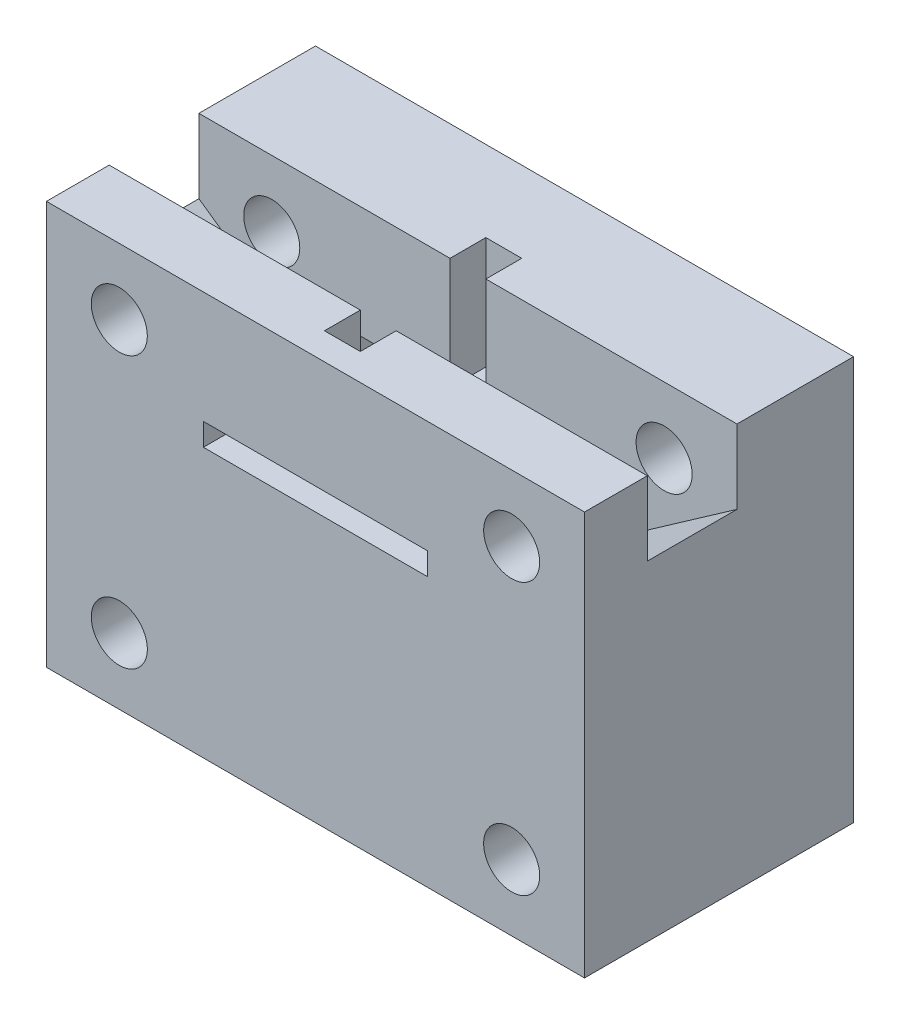
SolidWorks part; units mm, degrees
ref_plane "Front Plane" through (0, 0, 0) normal (0, 0, 1) x (1, 0, 0)
ref_plane "Top Plane" through (0, 0, 0) normal (0, 1, 0) x (1, 0, 0)
ref_plane "Right Plane" through (0, 0, 0) normal (1, 0, 0) x (0, 0, -1)
sketch "Sketch1" plane through (0, 0, 0) normal (0, 0, 1) x (1, 0, 0)
  line L0 (60, 0) -> (60, 97.0379) construction
  line L1 (0, 0) -> (120, 0)
  line L2 (0, 0) -> (0, 90)
  line L3 (0, 90) -> (120, 90)
  line L4 (120, 0) -> (120, 90)
  line L5 (0, 45) -> (130.8057, 45) construction
  line L6 (16.25, 75.25) -> (103.75, 75.25) construction
  line L7 (16.25, 75.25) -> (16.25, 14.75) construction
  circle A0 centre (16.25, 75.25) radius 3.25
  circle A1 centre (103.75, 75.25) radius 3.25
  circle A2 centre (103.75, 14.75) radius 3.25
  circle A3 centre (16.25, 14.75) radius 3.25
  dimension "D5" = 6.5
  dimension "D1" = 120
  dimension "D2" = 90
  dimension "D3" = 87.5
  dimension "D4" = 60.5
extrude "Boss-Extrude1" add sketch "Sketch1" along normal blind 60
sketch "Sketch2" plane through (0, 90, 0) normal (0, 1, 0) x (1, 0, 0)
  line L0 (120, -60) -> (120, 0) construction
  line L1 (0, 0) -> (120, 0)
  line L2 (0, 0) -> (0, -12)
  line L3 (0, -12) -> (120, -12)
  line L4 (120, 0) -> (120, -12)
  line L5 (0, -12) -> (0, -60)
  line L6 (0, -36) -> (120, -36) construction
  line L7 (45, -46) -> (45, -26)
  line L8 (45, -46) -> (75, -46)
  line L9 (45, -26) -> (75, -26)
  line L10 (75, -46) -> (75, -26)
  line L11 (45, -46) -> (75, -26) construction
  line L12 (45, -26) -> (75, -46) construction
  line L22 (56, -18) -> (64, -18)
  line L23 (56, -46) -> (64, -46)
  line L24 (56, -46) -> (56, -54)
  line L25 (56, -54) -> (64, -54)
  line L26 (64, -46) -> (64, -54)
  line L27 (64, -26) -> (64, -18)
  line L28 (56, -26) -> (64, -26)
  line L29 (56, -26) -> (56, -18)
  point P12 (60, -36)
  point P20 (60, -46)
  dimension "D1" = 12
  dimension "D2" = 30
  dimension "D3" = 20
  dimension "D4" = 8
  dimension "D5" = 8
extrude "Cut-Extrude1" cut sketch "Sketch2" against normal blind 30 contours L8 L10 L9 L7 | L29 L9 L27 L22 | L26 L8 L24 L25 region at (60, 90, 36) region at (60, 90, 50) region at (60, 90, 22)
sketch "Sketch3" plane through (0, 0, 60) normal (0, 0, 1) x (1, 0, 0)
  line L0 (120, 0) -> (120, 90) construction
  line L1 (0, 90) -> (120, 90)
  line L2 (0, 90) -> (0, 60)
  line L3 (0, 60) -> (120, 60)
  line L4 (120, 90) -> (120, 60)
  line L5 (0, 68) -> (120, 68)
  line L6 (64.25, 90) -> (55.75, 90)
  line L7 (64.25, 90) -> (64.25, 60)
  line L8 (64.25, 60) -> (55.75, 60)
  line L9 (55.75, 90) -> (55.75, 60)
  line L10 (45, 60) -> (56, 60) construction
  line L11 (35, 65) -> (85, 65)
  line L12 (35, 65) -> (35, 60)
  line L13 (35, 60) -> (85, 60)
  line L14 (85, 65) -> (85, 60)
  point P11 (60, 90)
  point P19 (60, 60)
  dimension "D2" = 8.5
  dimension "D3" = 8
  dimension "D4" = 50
  dimension "D5" = 5
extrude "Cut-Extrude2" cut sketch "Sketch3" against normal up to surface (14 mm away) contours L14 L11 L7 L3 | L11 L12 L3 L9 | L12 L11 L14 L13 region at (45.375, 62.5, 60) region at (74.625, 62.5, 60) up to face at (50.5, 75, 46)
ref_plane "Plane1" through (0, 0, 36) normal (0, 0, 1) x (1, 0, 0)
sketch "Sketch5" plane through (0, 0, 0) normal (0, 0, -1) x (-1, 0, 0)
  line L0 (-35, 65) -> (-35, 60) construction
  line L1 (-35, 65) -> (-85, 65) construction
  line L2 (-85, 65) -> (-85, 60) construction
  line L3 (-35, 60) -> (-85, 60) construction
  line L4 (0, 0) -> (0, 90)
  line L5 (0, 90) -> (-120, 90)
  line L6 (-120, 90) -> (-120, 0)
  line L7 (-120, 0) -> (0, 0)
  line L8 (0, 0) -> (0, 90)
  line L9 (0, 90) -> (-120, 90)
  line L10 (-120, 90) -> (-120, 0)
  line L11 (-120, 0) -> (0, 0)
  line L12 (-35, 65) -> (-35, 60)
  line L13 (-35, 65) -> (-85, 65)
  line L14 (-85, 65) -> (-85, 60)
  line L15 (-35, 60) -> (-85, 60)
  dimension "D1" = 0
extrude "Cut-Extrude5" cut sketch "Sketch5" against normal up to surface (26 mm away) contours L15 L12 L13 L14 region at (60, 62.5, 0) up to face at (69.5, 75, 26)
sketch "Sketch6" plane through (0, 60, 0) normal (0, 1, 0) x (1, 0, 0)
  line L1 (45, -26) -> (75, -26)
  line L2 (45, -26) -> (45, -46)
  line L3 (45, -46) -> (75, -46)
  line L4 (75, -26) -> (75, -46)
extrude "Cut-Extrude6" cut sketch "Sketch6" against normal blind 18
sketch "Sketch7" plane through (0, 0, 26) normal (0, 0, 1) x (1, 0, 0)
  line L0 (75, 42) -> (120, 73.5093)
  line L1 (120, 0) -> (120, 90) construction
  line L2 (120, 42) -> (138.0601, 42) construction
  line L3 (0, 90) -> (0, 73.5093)
  line L5 (60, 63.8) -> (60, 175.0062) construction
  line L6 (0, 90) -> (120, 90)
  line L7 (60, 90) -> (60, 42)
  line L8 (45, 42) -> (75, 42)
  line L9 (120, 90) -> (120, 73.5093)
  line L10 (45, 42) -> (0, 73.5093)
  line M5 (64, 65) -> (75, 65)
  line M6 (75, 65) -> (75, 90)
  line M8 (64, 90) -> (64, 65)
  dimension "D1" = 35
extrude "Cut-Extrude7" cut sketch "Sketch7" along normal up to surface (20 mm away) contours L10 L8 L7 L6 L3 | L9 L6 L7 L8 L0 M6 M5 M8 region at (87.3646, 69.3788, 26) region at (34.8983, 70.4075, 26) up to face at (50.5, 77.5, 46)
sketch "Sketch8" plane through (0, 0, 60) normal (0, 0, 1) x (1, 0, 0)
  line L0 (0, 45) -> (120, 45)
  line L1 (0, 90) -> (0, 0) construction
  line L2 (120, 0) -> (120, 90) construction
  line L3 (60, 0) -> (60, 90)
  line L4 (0, 0) -> (120, 0) construction
  line L5 (120, 90) -> (0, 90) construction
  circle A0 centre (16.25, 75.25) radius 6.25
  circle A1 centre (16.25, 75.25) radius 3.25 construction
  circle A2 centre (103.75, 75.25) radius 6.25
  circle A3 centre (103.75, 14.75) radius 6.25
  circle A4 centre (16.25, 14.75) radius 6.25
  circle M8 centre (16.25, 75.25) radius 3.25
  dimension "D1" = 12.5
extrude "Cut-Extrude8" cut sketch "Sketch8" against normal offset from surface (50 mm away) 10 contours A0 M8 | A2 | A3 | A4 region at (10.1768, 75.25, 60) up to face at (107, 14.75, 0)
